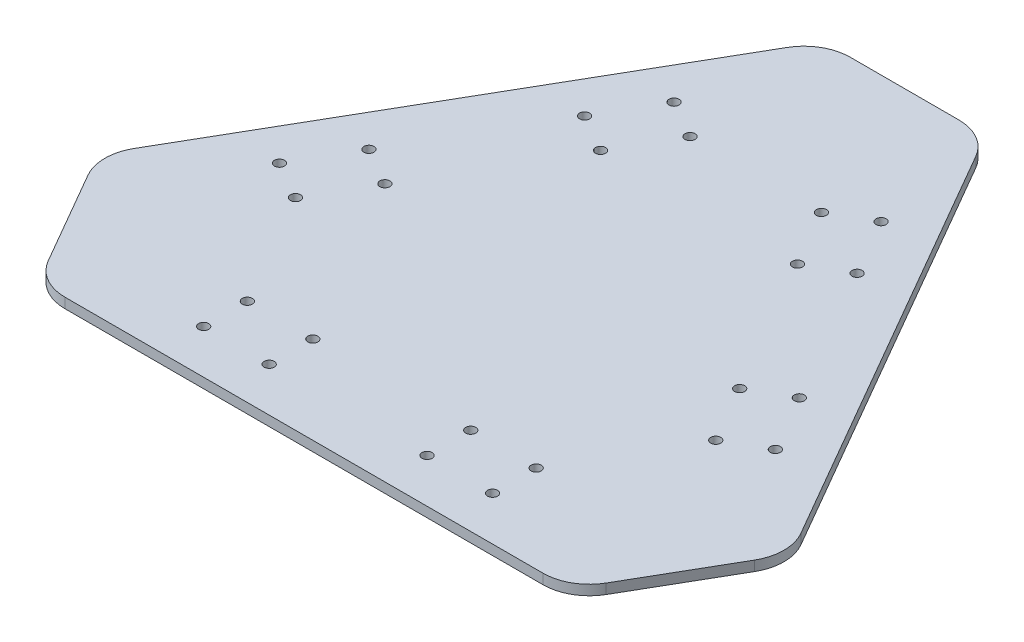
SolidWorks part; units mm, degrees
ref_plane "Front Plane" through (0, 0, 0) normal (0, 0, 1) x (1, 0, 0)
ref_plane "Top Plane" through (0, 0, 0) normal (0, 1, 0) x (1, 0, 0)
ref_plane "Right Plane" through (0, 0, 0) normal (1, 0, 0) x (0, 0, -1)
sketch "Sketch1" plane through (0, 0, 0) normal (0, 1, 0) x (1, 0, 0)
  line L0 (-22.2653, 97.1769) -> (22.2653, 97.1769)
  line L1 (22.2653, 97.1769) -> (95.2903, -29.3061)
  line L2 (95.2903, -29.3061) -> (73.025, -67.8708)
  line L3 (73.025, -67.8708) -> (-73.025, -67.8708)
  line L4 (-73.025, -67.8708) -> (-95.2903, -29.3061)
  line L5 (-95.2903, -29.3061) -> (-22.2653, 97.1769)
  circle A0 centre (0, 0) radius 99.695 construction
  dimension "D1" = 199.39
  dimension "D2" = 146.05
extrude "Boss-Extrude1" add sketch "Sketch1" along normal blind 2.75
sketch "Sketch2" plane through (0, 2.75, 0) normal (0, 1, 0) x (1, 0, 0)
  line L1 (-17.9917, -58.6934) -> (-6.35, -58.6934)
  line L2 (-17.9917, -58.6934) -> (-17.9917, -56.0518)
  line L3 (-17.9917, -56.0518) -> (-6.35, -56.0518)
  line L4 (-6.35, -58.6934) -> (-6.35, -56.0518)
  line L5 (-6.35, -56.0518) -> (6.35, -56.0518) construction
  line L6 (6.35, -58.6934) -> (17.9917, -58.6934)
  line L7 (6.35, -58.6934) -> (6.35, -56.0518)
  line L8 (6.35, -56.0518) -> (17.9917, -56.0518)
  line L9 (17.9917, -58.6934) -> (17.9917, -56.0518)
  line L10 (0, -56.0518) -> (0, 0) construction
  line L11 (-17.9917, -56.0518) -> (-79.8487, -56.0518) construction
  line L12 (-1.3208, -38.5004) -> (1.3208, -38.5004)
  line L13 (-1.3208, -38.5004) -> (-1.3208, -45.9934)
  line L14 (-1.3208, -45.9934) -> (1.3208, -45.9934)
  line L15 (1.3208, -38.5004) -> (1.3208, -45.9934)
  line L16 (-1.3208, -38.5004) -> (1.3208, -45.9934) construction
  line L17 (-1.3208, -45.9934) -> (1.3208, -38.5004) construction
  line L18 (-1.3208, -20.8474) -> (1.3208, -20.8474)
  line L19 (-1.3208, -20.8474) -> (-1.3208, -28.3404)
  line L20 (-1.3208, -28.3404) -> (1.3208, -28.3404)
  line L21 (1.3208, -20.8474) -> (1.3208, -28.3404)
  line L22 (-1.3208, -20.8474) -> (1.3208, -28.3404) construction
  line L23 (-1.3208, -28.3404) -> (1.3208, -20.8474) construction
  line L24 (-95.2903, -29.3061) -> (-73.025, -67.8708) construction
  line L25 (17.9917, -56.0518) -> (79.8487, -56.0518) construction
  line L26 (73.025, -67.8708) -> (95.2903, -29.3061) construction
  line L27 (-78.3235, -58.6934) -> (78.3235, -58.6934) construction
  line L28 (-55.0333, -57.3726) -> (-42.3333, -57.3726) construction
  line L29 (-30.6917, -56.0518) -> (-42.3333, -56.0518)
  line L30 (-30.6917, -56.0518) -> (-30.6917, -58.6934)
  line L31 (-30.6917, -58.6934) -> (-42.3333, -58.6934)
  line L32 (-42.3333, -56.0518) -> (-42.3333, -58.6934)
  line L33 (-55.0333, -56.0518) -> (-66.675, -56.0518)
  line L34 (-55.0333, -56.0518) -> (-55.0333, -58.6934)
  line L35 (-55.0333, -58.6934) -> (-66.675, -58.6934)
  line L36 (-66.675, -56.0518) -> (-66.675, -58.6934)
  line L37 (30.6917, -56.0518) -> (42.3333, -56.0518)
  line L38 (30.6917, -56.0518) -> (30.6917, -58.6934)
  line L39 (30.6917, -58.6934) -> (42.3333, -58.6934)
  line L40 (42.3333, -56.0518) -> (42.3333, -58.6934)
  line L41 (55.0333, -56.0518) -> (66.675, -56.0518)
  line L42 (55.0333, -56.0518) -> (55.0333, -58.6934)
  line L43 (55.0333, -58.6934) -> (66.675, -58.6934)
  line L44 (66.675, -56.0518) -> (66.675, -58.6934)
  line L45 (-30.6917, -57.3726) -> (-17.9917, -57.3726) construction
  line L46 (-6.35, -57.3726) -> (6.35, -57.3726) construction
  line L47 (17.9917, -57.3726) -> (30.6917, -57.3726) construction
  line L48 (42.3333, -57.3726) -> (55.0333, -57.3726) construction
  point P13 (0, -42.2469)
  point P18 (0, -24.5939)
  dimension "D1" = 12.7
  dimension "D3" = 12.7
  dimension "D4" = 7.493
  dimension "D5" = 2.6416
  dimension "D6" = 133.35
  dimension "D7" = 10.16
  dimension "D8" = 56.0518
extrude "Cut-Extrude1" [suppressed] cut sketch "Sketch2" against normal through all
sketch "Sketch3" [suppressed] plane through (0, 2.75, 0) normal (0, 1, 0) x (1, 0, 0)
  circle A0 centre (-17.9917, -56.0518) radius 0.1651
  circle A1 centre (-6.35, -56.0518) radius 0.1651
  circle A2 centre (6.35, -56.0518) radius 0.1651
  circle A3 centre (17.9917, -56.0518) radius 0.1651
  circle A4 centre (-1.3208, -45.9934) radius 0.1651
  circle A5 centre (1.3208, -45.9934) radius 0.1651
  circle A6 centre (-1.3208, -38.5004) radius 0.1651
  circle A7 centre (1.3208, -38.5004) radius 0.1651
  circle A8 centre (-1.3208, -28.3404) radius 0.1651
  circle A9 centre (1.3208, -28.3404) radius 0.1651
  circle A10 centre (-1.3208, -20.8474) radius 0.1651
  circle A11 centre (1.3208, -20.8474) radius 0.1651
  circle A12 centre (-17.9917, -58.6934) radius 0.1651
  circle A13 centre (-6.35, -58.6934) radius 0.1651
  circle A14 centre (6.35, -58.6934) radius 0.1651
  circle A15 centre (17.9917, -58.6934) radius 0.1651
  circle A16 centre (-30.6917, -56.0518) radius 0.1651
  circle A17 centre (-30.6917, -58.6934) radius 0.1651
  circle A18 centre (-42.3333, -58.6934) radius 0.1651
  circle A19 centre (-42.3333, -56.0518) radius 0.1651
  circle A20 centre (-55.0333, -56.0518) radius 0.1651
  circle A21 centre (-55.0333, -58.6934) radius 0.1651
  circle A22 centre (-66.675, -58.6934) radius 0.1651
  circle A23 centre (-66.675, -56.0518) radius 0.1651
  circle A24 centre (30.6917, -56.0518) radius 0.1651
  circle A25 centre (30.6917, -58.6934) radius 0.1651
  circle A26 centre (42.3333, -56.0518) radius 0.1651
  circle A27 centre (42.3333, -58.6934) radius 0.1651
  circle A28 centre (55.0333, -56.0518) radius 0.1651
  circle A29 centre (55.0333, -58.6934) radius 0.1651
  circle A30 centre (66.675, -56.0518) radius 0.1651
  circle A31 centre (66.675, -58.6934) radius 0.1651
  dimension "D1" = 0.3302
extrude "Cut-Extrude2" [suppressed] cut sketch "Sketch3" against normal through all
ref_axis "Axis1" through (0, 0, 0) along (0, 1, 0)
pattern_circular "CirPattern1" [suppressed] count 3 every 120 about axis through (0, 0, 0) along (0, 1, 0) of bodies 104
fillet "Fillet1" radius 12.7 6 edges at (-22.2653, 1.375, -97.1769) (22.2653, 1.375, -97.1769) (95.2903, 1.375, 29.3061) (73.025, 1.375, 67.8708) (-95.2903, 1.375, 29.3061) (-73.025, 1.375, 67.8708)
sketch "Sketch4" [suppressed] plane through (0, 2.75, 0) normal (0, 1, 0) x (1, 0, 0)
  line L0 (0, 83.0059) -> (0, 0) construction
  line L1 (-76.2, -43.9941) -> (76.2, -43.9941) construction
  line L2 (-76.2, -43.9941) -> (0, 83.0059) construction
  line L3 (0, 83.0059) -> (76.2, -43.9941) construction
  line L4 (60.8542, -56.0518) -> (76.2, -43.9941) construction
  line L5 (76.2, -43.9941) -> (78.9694, -24.6753) construction
  line L6 (66.5099, -56.0518) -> (55.1984, -56.0518) construction
  line L7 (76.1415, -19.7773) -> (81.7973, -29.5734) construction
  circle A0 centre (0, 83.0059) radius 1.8415
  circle A1 centre (-76.2, -43.9941) radius 1.8415
  circle A2 centre (76.2, -43.9941) radius 1.8415
  dimension "D1" = 3.683
  dimension "D2" = 152.4
  dimension "D3" = 127
extrude "Cut-Extrude3" [suppressed] cut sketch "Sketch4" against normal through all
sketch "Sketch5" plane through (0, 2.75, 0) normal (0, 1, 0) x (1, 0, 0)
  line L0 (-65.6927, -67.8708) -> (65.6927, -67.8708) construction
  circle A0 centre (21.7, -43.7757) radius 1.3891
  circle A1 centre (21.7, -55.7757) radius 1.3891
  circle A2 centre (39.7, -43.7757) radius 1.3891
  circle A3 centre (39.7, -55.7757) radius 1.3891
  dimension "D1" = 24.0951
  dimension "D3" = 2.7781
  dimension "D4" = 2.7781
  dimension "D6" = 2.7781
  dimension "D7" = 2.7781
  dimension "D2" = 21.7
  dimension "D5" = 12
  dimension "D8" = 18
extrude "Cut-Extrude4" cut sketch "Sketch5" against normal through all
mirror "Mirror1" about plane through (0, 0, 0) normal (1, 0, 0) of "Cut-Extrude4"
pattern_circular "CirPattern2" count 3 over 360 about axis through (0, 0, 0) along (0, 1, 0) of "Cut-Extrude4", "Mirror1"
